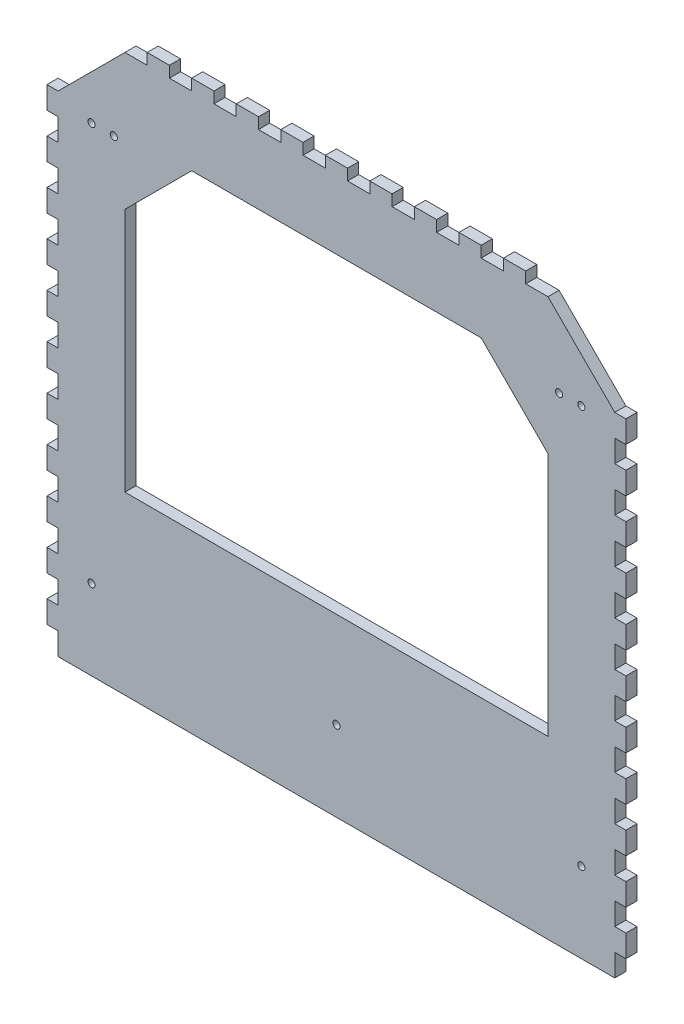
SolidWorks part; units mm, degrees
material "Buche"
ref_plane "Ebene vorne" through (0, 0, 0) normal (0, 0, 1) x (1, 0, 0)
ref_plane "Ebene oben" through (0, 0, 0) normal (0, 1, 0) x (1, 0, 0)
ref_plane "Ebene rechts" through (0, 0, 0) normal (1, 0, 0) x (0, 0, -1)
sketch "Skizze1" plane through (0, 0, 0) normal (0, 0, 1) x (1, 0, 0)
  line L0 (35, 250) -> (45, 250)
  line L1 (45, 250) -> (45, 255)
  line L2 (45, 255) -> (55, 255)
  line L3 (55, 255) -> (55, 250)
  line L4 (55, 250) -> (65, 250)
  line L5 (65, 250) -> (65, 255)
  line L6 (65, 255) -> (75, 255)
  line L7 (75, 255) -> (75, 250)
  line L8 (75, 250) -> (85, 250)
  line L9 (85, 250) -> (85, 255)
  line L10 (85, 255) -> (95, 255)
  line L11 (95, 255) -> (95, 250)
  line L12 (95, 250) -> (105, 250)
  line L13 (105, 250) -> (105, 255)
  line L14 (105, 255) -> (115, 255)
  line L15 (115, 255) -> (115, 250)
  line L16 (115, 250) -> (125, 250)
  line L17 (125, 250) -> (125, 255)
  line L18 (125, 255) -> (135, 255)
  line L19 (135, 255) -> (135, 250)
  line L20 (135, 250) -> (145, 250)
  line L21 (145, 250) -> (145, 255)
  line L22 (145, 255) -> (155, 255)
  line L23 (155, 255) -> (155, 250)
  line L24 (155, 250) -> (165, 250)
  line L25 (165, 250) -> (165, 255)
  line L26 (165, 255) -> (175, 255)
  line L27 (175, 255) -> (175, 250)
  line L28 (175, 250) -> (185, 250)
  line L29 (185, 250) -> (185, 255)
  line L30 (185, 255) -> (195, 255)
  line L31 (195, 255) -> (195, 250)
  line L32 (195, 250) -> (205, 250)
  line L33 (205, 250) -> (205, 255)
  line L34 (205, 255) -> (215, 255)
  line L35 (215, 255) -> (215, 250)
  line L36 (215, 250) -> (225, 250)
  line L197 (255, 220) -> (260, 220)
  line L198 (260, 220) -> (260, 210)
  line L199 (5, 190) -> (5, 180)
  line L200 (65, 218.9712) -> (195, 218.9712)
  line L201 (255, 210) -> (255, 200)
  line L202 (255, 200) -> (260, 200)
  line L203 (260, 200) -> (260, 190)
  line L204 (5, 200) -> (0, 200)
  line L205 (5, 210) -> (5, 200)
  line L206 (0, 190) -> (5, 190)
  line L207 (35, 78.9712) -> (35, 188.9712)
  line L208 (255, 190) -> (255, 180)
  line L209 (260, 190) -> (255, 190)
  line L210 (0, 200) -> (0, 190)
  line L211 (5, 170) -> (5, 160)
  line L212 (5, 180) -> (0, 180)
  line L213 (0, 170) -> (5, 170)
  line L214 (5, 220) -> (35, 250)
  line L215 (255, 180) -> (260, 180)
  line L216 (260, 180) -> (260, 170)
  line L217 (255, 170) -> (255, 160)
  line L218 (0, 180) -> (0, 170)
  line L219 (5, 220) -> (0, 220)
  line L220 (260, 170) -> (255, 170)
  line L221 (255, 160) -> (260, 160)
  line L222 (5, 150) -> (5, 140)
  line L223 (5, 160) -> (0, 160)
  line L224 (225, 188.9712) -> (195, 218.9712)
  line L225 (260, 160) -> (260, 150)
  line L226 (255, 150) -> (255, 140)
  line L227 (260, 150) -> (255, 150)
  line L228 (0, 150) -> (5, 150)
  line L229 (0, 160) -> (0, 150)
  line L230 (255, 140) -> (260, 140)
  line L231 (260, 140) -> (260, 130)
  line L232 (260, 210) -> (255, 210)
  line L233 (5, 130) -> (5, 120)
  line L234 (5, 140) -> (0, 140)
  line L235 (0, 210) -> (5, 210)
  line L236 (0, 130) -> (5, 130)
  line L237 (255, 130) -> (255, 120)
  line L238 (0, 140) -> (0, 130)
  line L239 (5, 110) -> (5, 100)
  line L240 (5, 120) -> (0, 120)
  line L241 (35, 78.9712) -> (225, 78.9712)
  line L242 (260, 130) -> (255, 130)
  line L243 (255, 120) -> (260, 120)
  line L244 (260, 120) -> (260, 110)
  line L245 (255, 110) -> (255, 100)
  line L246 (260, 110) -> (255, 110)
  line L247 (0, 110) -> (5, 110)
  line L248 (0, 120) -> (0, 110)
  line L249 (5, 90) -> (5, 80)
  line L250 (5, 100) -> (0, 100)
  line L251 (0, 90) -> (5, 90)
  line L252 (5, 0) -> (255, 0)
  line L253 (35, 188.9712) -> (65, 218.9712)
  line L254 (255, 100) -> (260, 100)
  line L255 (260, 100) -> (260, 90)
  line L256 (255, 90) -> (255, 80)
  line L257 (260, 90) -> (255, 90)
  line L258 (255, 80) -> (260, 80)
  line L259 (260, 80) -> (260, 70)
  line L260 (0, 100) -> (0, 90)
  line L261 (5, 70) -> (5, 60)
  line L262 (255, 70) -> (255, 60)
  line L263 (225, 78.9712) -> (225, 188.9712)
  line L264 (260, 70) -> (255, 70)
  line L265 (5, 80) -> (0, 80)
  line L266 (0, 70) -> (5, 70)
  line L267 (0, 80) -> (0, 70)
  line L268 (5, 50) -> (5, 40)
  line L269 (255, 60) -> (260, 60)
  line L270 (260, 60) -> (260, 50)
  line L271 (255, 50) -> (255, 40)
  line L272 (5, 60) -> (0, 60)
  line L273 (0, 50) -> (5, 50)
  line L274 (255, 220) -> (225, 250)
  line L275 (260, 50) -> (255, 50)
  line L276 (255, 40) -> (260, 40)
  line L277 (0, 60) -> (0, 50)
  line L278 (5, 30) -> (5, 20)
  line L279 (0, 220) -> (0, 210)
  line L280 (5, 40) -> (0, 40)
  line L281 (260, 40) -> (260, 30)
  line L282 (255, 30) -> (255, 20)
  line L283 (260, 30) -> (255, 30)
  line L284 (255, 20) -> (260, 20)
  line L285 (260, 20) -> (260, 10)
  line L286 (0, 30) -> (5, 30)
  line L287 (255, 10) -> (255, 0)
  line L288 (260, 10) -> (255, 10)
  line L289 (0, 40) -> (0, 30)
  line L290 (5, 10) -> (5, 0)
  line L291 (5, 20) -> (0, 20)
  line L292 (0, 10) -> (5, 10)
  line L293 (0, 20) -> (0, 10)
  circle A0 centre (20, 215) radius 1.6
  circle A1 centre (30, 215) radius 1.6
  circle A2 centre (240, 215) radius 1.6
  circle A3 centre (230, 215) radius 1.6
  circle A4 centre (20, 36) radius 1.6
  circle A5 centre (130, 36) radius 1.6
  circle A6 centre (240, 36) radius 1.6
  point P3 (0, 0)
  dimension "D1" = 9
extrude "Aufsatz-Linear austragen2" add sketch "Skizze1" along normal blind 5
